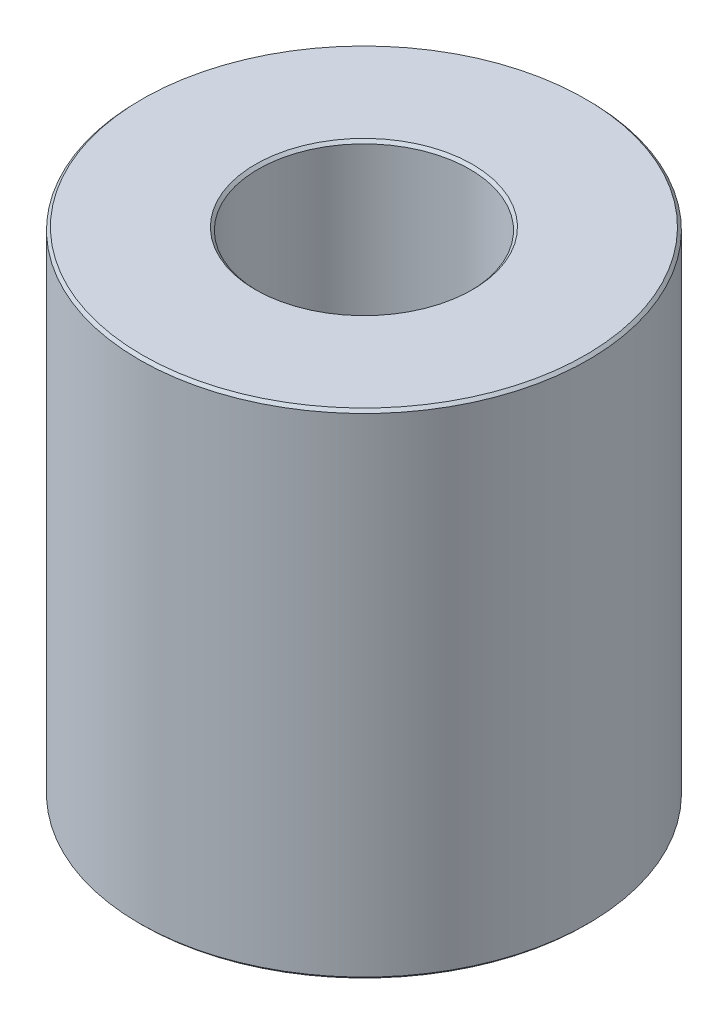
SolidWorks part; units mm, degrees
ref_plane "Front Plane" through (0, 0, 0) normal (0, 0, 1) x (1, 0, 0)
ref_plane "Top Plane" through (0, 0, 0) normal (0, 1, 0) x (1, 0, 0)
ref_plane "Right Plane" through (0, 0, 0) normal (1, 0, 0) x (0, 0, -1)
sketch "Sketch1" plane through (0, 0, 0) normal (0, 1, 0) x (1, 0, 0)
  circle A0 centre (0, 0) radius 25
  dimension "SLEEVE_OD" = 50
extrude "Boss-Extrude1" add sketch "Sketch1" along normal blind 54.974
sketch "Sketch2" plane through (0, 0, 0) normal (0, 1, 0) x (1, 0, 0)
  circle A0 centre (0, 0) radius 11.7836
  dimension "BORE_D" = 23.5673
extrude "Cut-Extrude1" cut sketch "Sketch2" along normal through all
chamfer "Chamfer1" distance 0.3095 angle 45 4 edges at (0, 54.974, 11.7836) (0, 0, 11.7836) (0, 0, 25) (0, 54.974, 25)
